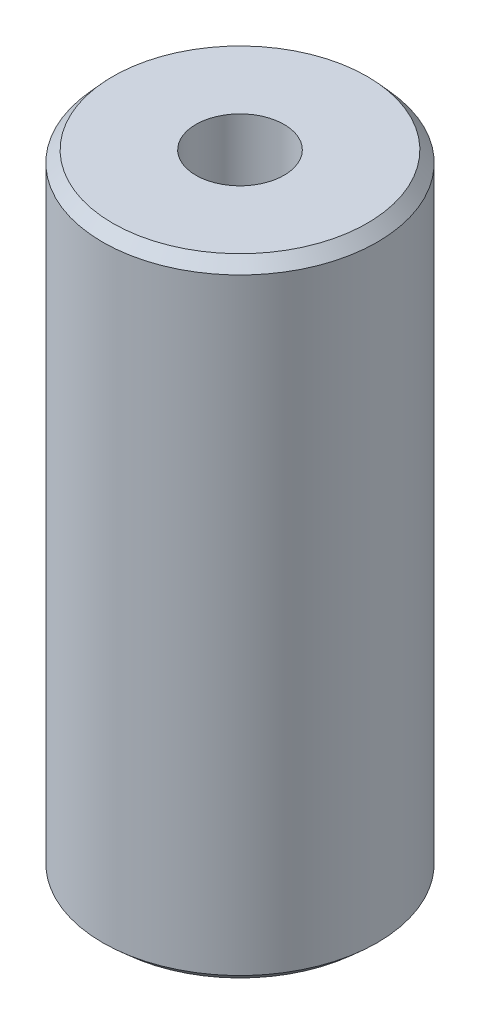
SolidWorks part; units mm, degrees
ref_plane "Front Plane" through (0, 0, 0) normal (0, 0, 1) x (1, 0, 0)
ref_plane "Top Plane" through (0, 0, 0) normal (0, 1, 0) x (1, 0, 0)
ref_plane "Right Plane" through (0, 0, 0) normal (1, 0, 0) x (0, 0, -1)
sketch "Sketch1" plane through (0, 0, 0) normal (0, 1, 0) x (1, 0, 0)
  circle A0 centre (0, 0) radius 7.5
  dimension "SHAFT_OD" = 15
extrude "Boss-Extrude1" add sketch "Sketch1" along normal blind 34.3035
sketch "Sketch2" plane through (0, 0, 0) normal (0, 1, 0) x (1, 0, 0)
  circle A0 centre (0, 0) radius 2.4085
  dimension "BORE_D" = 4.8171
extrude "Cut-Extrude1" cut sketch "Sketch2" along normal through all
chamfer "Chamfer1" distance 0.6164 angle 41.821 2 edges at (0, 34.3035, 7.5) (0, 0, 7.5) first distance on face at (0, 34.3035, 7.5) first distance on face at (0, 0, 2.4085)
